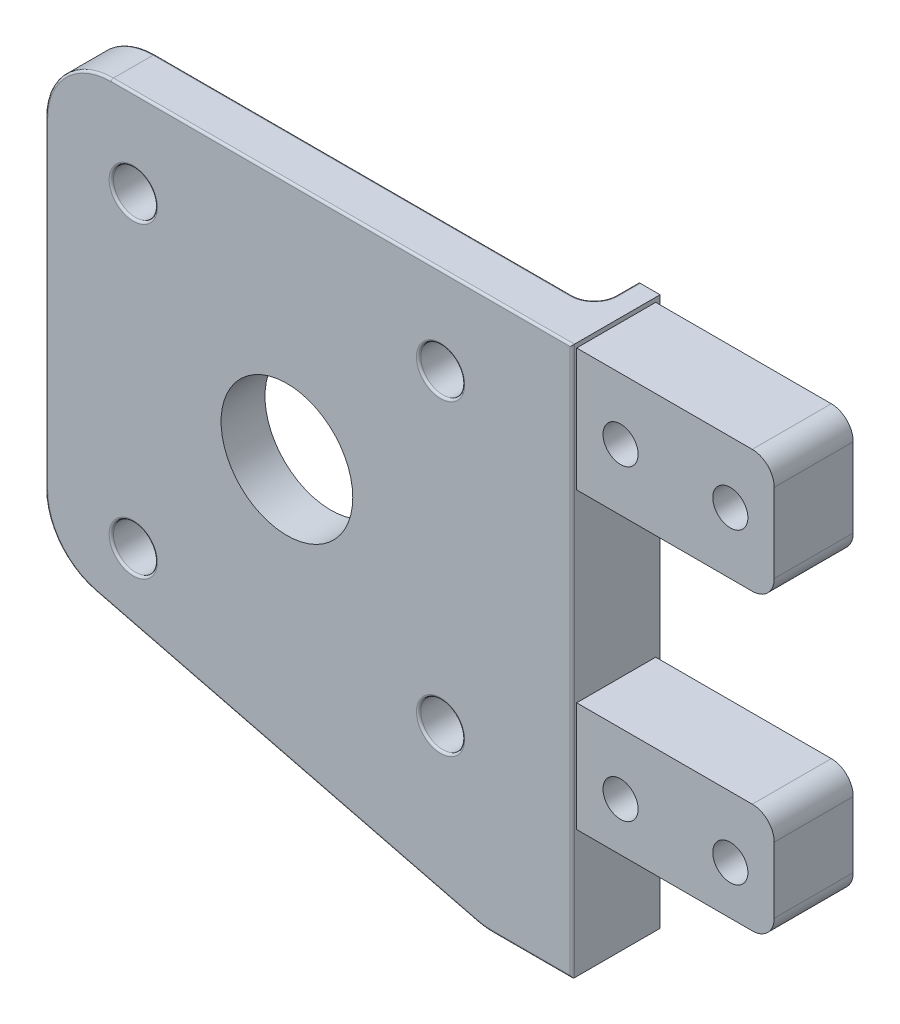
SolidWorks part; units mm, degrees
ref_plane "Ön Düzlem" through (0, 0, 0) normal (0, 0, 1) x (1, 0, 0)
ref_plane "Üst Düzlem" through (0, 0, 0) normal (0, 1, 0) x (1, 0, 0)
ref_plane "Sağ Düzlem" through (0, 0, 0) normal (1, 0, 0) x (0, 0, -1)
sketch "Sketch1" plane through (0, 0, 0) normal (0, 0, 1) x (1, 0, 0)
  line L0 (-120, 62.5) -> (0, 62.5)
  line L1 (0, 62.5) -> (0, -62.5)
  line L2 (0, -62.5) -> (-20, -62.5)
  line L3 (-20, -62.5) -> (-120, -37.5)
  line L4 (-120, -37.5) -> (-120, 62.5)
  line L5 (0, 61.5) -> (45, 61.5)
  line L6 (45, 61.5) -> (45, 33.5)
  line L7 (45, 33.5) -> (0, 33.5)
  line L8 (0, -8.5) -> (45, -8.5)
  line L9 (45, -8.5) -> (45, -33.5)
  line L10 (45, -33.5) -> (0, -33.5)
  line L11 (45, 47.5) -> (0, 47.5) construction
  circle A0 centre (-100, 42.5) radius 5
  circle A1 centre (-30, 42.5) radius 5
  circle A2 centre (-100, -27.5) radius 5
  circle A3 centre (-30, -27.5) radius 5
  circle A4 centre (10, 47.5) radius 4
  circle A5 centre (35, 47.5) radius 4
  circle A6 centre (10, -22.5) radius 4
  circle A7 centre (35, -22.5) radius 4
  dimension "D5" = 10
  dimension "D6" = 20
  dimension "D10" = 8
  dimension "D1" = 120
  dimension "D2" = 20
  dimension "D3" = 125
  dimension "D4" = 100
  dimension "D7" = 20
  dimension "D8" = 70
  dimension "D9" = 70
  dimension "D11" = 1
  dimension "D12" = 29
  dimension "D13" = 28
  dimension "D14" = 40
  dimension "D15" = 25
  dimension "D16" = 45
  dimension "D17" = 10
  dimension "D18" = 25
extrude "Boss-Extrude1" add sketch "Sketch1" along normal mid plane 10 contours L4 L3 L2 L1 L0 A3 A2 A1 A0 region at (-57.4022, 4.864, 0)
extrude "Boss-Extrude2" add sketch "Sketch1<3>" along normal offset from surface 1 and the other way blind 14 contours L11 L6 L5 L1 A4 A5 | L6 L11 A5 A4 L1 L7 | L10 L9 L8 L1 A7 A6 region at (22.5, 54.9597, 0) region at (22.5, 40.0403, 0) region at (22.5, -20.8528, 0) up to face at (-25, -27.5, 5)
sketch "Sketch1<3>" plane through (0, 0, 0) normal (0, 0, 1) x (1, 0, 0) same geometry as "Sketch1"
sketch "Sketch2" plane through (0, 0, -5) normal (0, 0, -1) x (-1, 0, 0)
  line L0 (0, 33.5) -> (0, -8.5) construction
  line L1 (0, 62.5) -> (5, 62.5)
  line L2 (0, 62.5) -> (0, -62.5)
  line L3 (0, -62.5) -> (5, -62.5)
  line L4 (5, 62.5) -> (5, -62.5)
  line L5 (0, 62.5) -> (5, -62.5) construction
  line L6 (0, -62.5) -> (5, 62.5) construction
  line L7 (0, -62.5) -> (20, -62.5) construction
  point P0 (2.5, 0)
  dimension "D1" = 5
extrude "Boss-Extrude3" add sketch "Sketch2" along normal blind 10
fillet "Fillet1" radius 5 5 edges at (45, -33.5, -5) (45, -8.5, -5) (45, 33.5, -5) (45, 61.5, -5) (-5, 0, -5)
fillet "Fillet2" radius 15 3 edges at (-20, -62.5, 0) (-120, -37.5, 0) (-120, 62.5, 0)
fillet "Fillet3" radius 0.5 27 edges at (-5, -62.5, -12.5) (-6.4645, -62.5, -6.4645) (-5, 62.5, -12.5) (-6.4645, 62.5, -6.4645) (-116.8231, -35.0195, 5) (-120, 10.8558, 5) (-115.6066, 58.1066, 5) (-52.5, 62.5, 5) (0, 0, 5) (-9.0767, -62.5, 5) (-19.9862, -62.3876, 5) (-65.2147, -51.1963, 5) (-95, 42.5, 5) (-25, 42.5, 5) (-95, -27.5, 5) (-25, -27.5, 5) (-57.5, 62.5, -5) (-115.6066, 58.1066, -5) (-120, 10.8558, -5) (-116.8231, -35.0195, -5) (-65.2147, -51.1963, -5) (-19.9862, -62.3876, -5) (-14.0767, -62.5, -5) (-25, -27.5, -5) (-95, -27.5, -5) (-25, 42.5, -5) (-95, 42.5, -5)
sketch "Sketch3" plane through (0, 0, 5) normal (0, 0, 1) x (1, 0, 0)
  line L0 (-100, -27.5) -> (-30, 42.5) construction
  line L1 (-100, 42.5) -> (-30, -27.5) construction
  circle A0 centre (-65, 7.5) radius 15
  dimension "D1" = 30
extrude "Cut-Extrude1" cut sketch "Sketch3" against normal up to next
